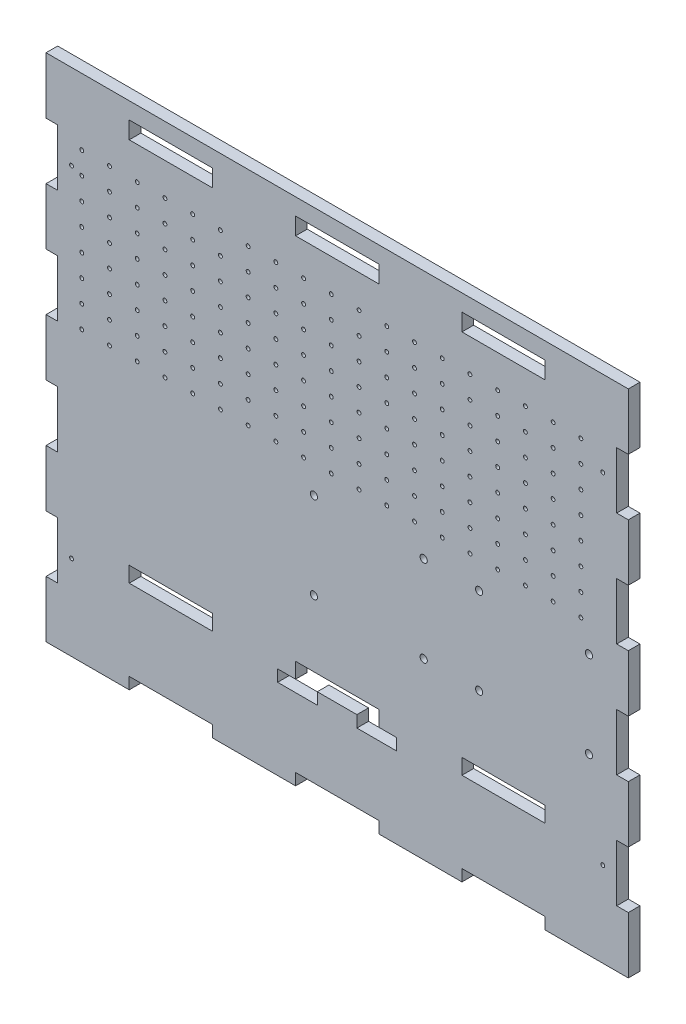
SolidWorks part; units mm, degrees
ref_plane "Front Plane" through (0, 0, 0) normal (0, 0, 1) x (1, 0, 0)
ref_plane "Top Plane" through (0, 0, 0) normal (0, 1, 0) x (1, 0, 0)
ref_plane "Right Plane" through (0, 0, 0) normal (1, 0, 0) x (0, 0, -1)
sketch "Sketch1" plane through (0, 0, 0) normal (0, 0, 1) x (1, 0, 0)
  line L1 (-127.8759, 139.2641) -> (138.8241, 139.2641)
  line L2 (-127.8759, 139.2641) -> (-127.8759, -84.2559)
  line L3 (-127.8759, -84.2559) -> (138.8241, -84.2559)
  line L4 (138.8241, 139.2641) -> (138.8241, -84.2559)
  dimension "D1" = 266.7
  dimension "D2" = 223.52
extrude "Boss-Extrude1" add sketch "Sketch1" along normal blind 5.334
sketch "Sketch2" plane through (0, 0, 5.334) normal (0, 0, 1) x (1, 0, 0)
  line L0 (-127.8759, -84.2559) -> (138.8241, -84.2559) construction
  line L1 (-89.7759, -84.2559) -> (-51.6759, -84.2559)
  line L2 (-89.7759, -84.2559) -> (-89.7759, -78.9219)
  line L3 (-89.7759, -78.9219) -> (-51.6759, -78.9219)
  line L4 (-51.6759, -84.2559) -> (-51.6759, -78.9219)
  line L5 (-89.7759, -78.9219) -> (-127.8759, -78.9219) construction
  line L6 (-13.5759, -84.2559) -> (24.5241, -84.2559)
  line L7 (-13.5759, -84.2559) -> (-13.5759, -78.9219)
  line L8 (-13.5759, -78.9219) -> (24.5241, -78.9219)
  line L9 (24.5241, -84.2559) -> (24.5241, -78.9219)
  line L10 (62.6241, -84.2559) -> (100.7241, -84.2559)
  line L11 (62.6241, -84.2559) -> (62.6241, -78.9219)
  line L12 (62.6241, -78.9219) -> (100.7241, -78.9219)
  line L13 (100.7241, -84.2559) -> (100.7241, -78.9219)
  line L14 (-127.8759, 139.2641) -> (-127.8759, -84.2559) construction
  line L15 (-51.6759, -78.9219) -> (-13.5759, -78.9219) construction
  line L16 (24.5241, -78.9219) -> (62.6241, -78.9219) construction
  line L17 (62.6241, -78.9219) -> (62.364, -79.7896) construction
  line L18 (100.7241, -78.9219) -> (138.8241, -78.9219) construction
  line L19 (138.8241, -84.2559) -> (138.8241, 139.2641) construction
  line L20 (-127.8759, 27.5041) -> (138.8241, 27.5041) construction
  line L21 (100.7241, 139.2641) -> (100.7241, 133.9301)
  line L22 (62.6241, 133.9301) -> (100.7241, 133.9301)
  line L23 (62.6241, 139.2641) -> (62.6241, 133.9301)
  line L24 (24.5241, 139.2641) -> (24.5241, 133.9301)
  line L25 (-13.5759, 133.9301) -> (24.5241, 133.9301)
  line L26 (-13.5759, 139.2641) -> (-13.5759, 133.9301)
  line L27 (-51.6759, 139.2641) -> (-51.6759, 133.9301)
  line L28 (-89.7759, 133.9301) -> (-51.6759, 133.9301)
  line L29 (-89.7759, 139.2641) -> (-89.7759, 133.9301)
  line L30 (62.6241, 139.2641) -> (100.7241, 139.2641)
  line L31 (-13.5759, 139.2641) -> (24.5241, 139.2641)
  line L32 (-89.7759, 139.2641) -> (-51.6759, 139.2641)
  dimension "D1" = 5.334
extrude "Cut-Extrude1" cut sketch "Sketch2" against normal through all
sketch "Sketch5" plane through (0, 0, 5.334) normal (0, 0, 1) x (1, 0, 0)
  line L0 (-51.6759, -34.8224) -> (-13.5759, -34.8224) construction
  line L1 (-89.7759, -34.8224) -> (-51.6759, -34.8224)
  line L2 (-89.7759, -34.8224) -> (-89.7759, -41.9344)
  line L3 (-89.7759, -41.9344) -> (-51.6759, -41.9344)
  line L4 (-51.6759, -34.8224) -> (-51.6759, -41.9344)
  line L5 (-13.5759, -34.8224) -> (24.5241, -34.8224)
  line L6 (-13.5759, -34.8224) -> (-13.5759, -41.9344)
  line L7 (-13.5759, -41.9344) -> (24.5241, -41.9344)
  line L8 (24.5241, -34.8224) -> (24.5241, -41.9344)
  line L9 (62.6241, -34.8224) -> (100.7241, -34.8224)
  line L10 (62.6241, -34.8224) -> (62.6241, -41.9344)
  line L11 (62.6241, -41.9344) -> (100.7241, -41.9344)
  line L12 (100.7241, -34.8224) -> (100.7241, -41.9344)
  line L13 (-51.6759, -41.9344) -> (-13.5759, -41.9344) construction
  line L14 (24.5241, -34.8224) -> (62.6241, -34.8224) construction
  line L15 (24.5241, -41.9344) -> (62.6241, -41.9344) construction
  line L16 (-89.7759, -34.8224) -> (-127.8759, -34.8224) construction
  line L17 (-127.8759, 139.2641) -> (-127.8759, -84.2559) construction
  line L18 (-89.7759, -41.9344) -> (-127.8759, -41.9344) construction
  line L19 (100.7241, -34.8224) -> (138.8241, -34.8224) construction
  line L20 (138.8241, -84.2559) -> (138.8241, 139.2641) construction
  line L21 (100.7241, -41.9344) -> (138.8241, -41.9344) construction
  dimension "D1" = 7.112
extrude "Cut-Extrude3" cut sketch "Sketch5" against normal through all
sketch "Sketch8" plane through (0, 0, 5.334) normal (0, 0, 1) x (1, 0, 0)
  line L0 (-13.5759, -41.9344) -> (24.5241, -41.9344) construction
  line L1 (-21.7977, -47.2684) -> (-3.6478, -47.2684)
  line L2 (-21.7977, -47.2684) -> (-21.7977, -41.9344)
  line L3 (-21.7977, -41.9344) -> (-3.6478, -41.9344)
  line L4 (-3.6478, -47.2684) -> (-3.6478, -41.9344)
  line L5 (-3.6478, -47.2684) -> (14.5022, -47.2684) construction
  line L6 (14.5022, -41.9344) -> (32.6521, -41.9344)
  line L7 (14.5022, -41.9344) -> (14.5022, -47.2684)
  line L8 (14.5022, -47.2684) -> (32.6521, -47.2684)
  line L9 (32.6521, -41.9344) -> (32.6521, -47.2684)
  line L10 (14.5022, -47.2684) -> (14.3218, -49.4005) construction
  line L11 (14.5022, -41.9344) -> (-3.6478, -41.9344) construction
  line L12 (62.6241, -34.8224) -> (62.6241, -41.9344) construction
  line L13 (-51.6759, -41.9344) -> (-51.6759, -34.8224) construction
  dimension "D1" = 5.334
  dimension "D2" = 29.972
  dimension "D3" = 29.8782
extrude "Cut-Extrude6" cut sketch "Sketch8" against normal through all
sketch "Sketch9" plane through (0, 0, 5.334) normal (0, 0, 1) x (1, 0, 0)
  line L0 (-111.5143, 118.9789) -> (-98.8143, 118.9789) construction
  line L1 (-111.5143, 108.8189) -> (-98.8143, 108.8189) construction
  line L2 (-111.5143, 98.6589) -> (-98.8143, 98.6589) construction
  line L3 (-111.5143, 88.4989) -> (-98.8143, 88.4989) construction
  line L4 (-111.5143, 78.3389) -> (-98.8143, 78.3389) construction
  line L5 (-111.5143, 68.1789) -> (-98.8143, 68.1789) construction
  line L6 (-111.5143, 58.0189) -> (-98.8143, 58.0189) construction
  line L7 (-111.5143, 47.8589) -> (-98.8143, 47.8589) construction
  line L8 (-111.5143, 118.9789) -> (-111.5143, 108.8189) construction
  circle A0 centre (-111.5143, 118.9789) radius 0.889
  circle A1 centre (-98.8143, 118.9789) radius 0.889
  circle A2 centre (-86.1143, 118.9789) radius 0.889
  circle A3 centre (-73.4143, 118.9789) radius 0.889
  circle A4 centre (-60.7143, 118.9789) radius 0.889
  circle A5 centre (-48.0143, 118.9789) radius 0.889
  circle A6 centre (-35.3143, 118.9789) radius 0.889
  circle A7 centre (-22.6143, 118.9789) radius 0.889
  circle A8 centre (-9.9143, 118.9789) radius 0.889
  circle A9 centre (2.7857, 118.9789) radius 0.889
  circle A10 centre (15.4857, 118.9789) radius 0.889
  circle A11 centre (28.1857, 118.9789) radius 0.889
  circle A12 centre (40.8857, 118.9789) radius 0.889
  circle A13 centre (53.5857, 118.9789) radius 0.889
  circle A14 centre (66.2857, 118.9789) radius 0.889
  circle A15 centre (78.9857, 118.9789) radius 0.889
  circle A16 centre (91.6857, 118.9789) radius 0.889
  circle A17 centre (104.3857, 118.9789) radius 0.889
  circle A18 centre (117.0857, 118.9789) radius 0.889
  circle A19 centre (-111.5143, 108.8189) radius 0.889
  circle A20 centre (-98.8143, 108.8189) radius 0.889
  circle A21 centre (-86.1143, 108.8189) radius 0.889
  circle A22 centre (-73.4143, 108.8189) radius 0.889
  circle A23 centre (-60.7143, 108.8189) radius 0.889
  circle A24 centre (-48.0143, 108.8189) radius 0.889
  circle A25 centre (-35.3143, 108.8189) radius 0.889
  circle A26 centre (-22.6143, 108.8189) radius 0.889
  circle A27 centre (-9.9143, 108.8189) radius 0.889
  circle A28 centre (2.7857, 108.8189) radius 0.889
  circle A29 centre (15.4857, 108.8189) radius 0.889
  circle A30 centre (28.1857, 108.8189) radius 0.889
  circle A31 centre (40.8857, 108.8189) radius 0.889
  circle A32 centre (53.5857, 108.8189) radius 0.889
  circle A33 centre (66.2857, 108.8189) radius 0.889
  circle A34 centre (78.9857, 108.8189) radius 0.889
  circle A35 centre (91.6857, 108.8189) radius 0.889
  circle A36 centre (104.3857, 108.8189) radius 0.889
  circle A37 centre (117.0857, 108.8189) radius 0.889
  circle A38 centre (-111.5143, 98.6589) radius 0.889
  circle A39 centre (-98.8143, 98.6589) radius 0.889
  circle A40 centre (-86.1143, 98.6589) radius 0.889
  circle A41 centre (-73.4143, 98.6589) radius 0.889
  circle A42 centre (-60.7143, 98.6589) radius 0.889
  circle A43 centre (-48.0143, 98.6589) radius 0.889
  circle A44 centre (-35.3143, 98.6589) radius 0.889
  circle A45 centre (-22.6143, 98.6589) radius 0.889
  circle A46 centre (-9.9143, 98.6589) radius 0.889
  circle A47 centre (2.7857, 98.6589) radius 0.889
  circle A48 centre (15.4857, 98.6589) radius 0.889
  circle A49 centre (28.1857, 98.6589) radius 0.889
  circle A50 centre (40.8857, 98.6589) radius 0.889
  circle A51 centre (53.5857, 98.6589) radius 0.889
  circle A52 centre (66.2857, 98.6589) radius 0.889
  circle A53 centre (78.9857, 98.6589) radius 0.889
  circle A54 centre (91.6857, 98.6589) radius 0.889
  circle A55 centre (104.3857, 98.6589) radius 0.889
  circle A56 centre (117.0857, 98.6589) radius 0.889
  circle A57 centre (-111.5143, 88.4989) radius 0.889
  circle A58 centre (-98.8143, 88.4989) radius 0.889
  circle A59 centre (-86.1143, 88.4989) radius 0.889
  circle A60 centre (-73.4143, 88.4989) radius 0.889
  circle A61 centre (-60.7143, 88.4989) radius 0.889
  circle A62 centre (-48.0143, 88.4989) radius 0.889
  circle A63 centre (-35.3143, 88.4989) radius 0.889
  circle A64 centre (-22.6143, 88.4989) radius 0.889
  circle A65 centre (-9.9143, 88.4989) radius 0.889
  circle A66 centre (2.7857, 88.4989) radius 0.889
  circle A67 centre (15.4857, 88.4989) radius 0.889
  circle A68 centre (28.1857, 88.4989) radius 0.889
  circle A69 centre (40.8857, 88.4989) radius 0.889
  circle A70 centre (53.5857, 88.4989) radius 0.889
  circle A71 centre (66.2857, 88.4989) radius 0.889
  circle A72 centre (78.9857, 88.4989) radius 0.889
  circle A73 centre (91.6857, 88.4989) radius 0.889
  circle A74 centre (104.3857, 88.4989) radius 0.889
  circle A75 centre (117.0857, 88.4989) radius 0.889
  circle A76 centre (-111.5143, 78.3389) radius 0.889
  circle A77 centre (-98.8143, 78.3389) radius 0.889
  circle A78 centre (-86.1143, 78.3389) radius 0.889
  circle A79 centre (-73.4143, 78.3389) radius 0.889
  circle A80 centre (-60.7143, 78.3389) radius 0.889
  circle A81 centre (-48.0143, 78.3389) radius 0.889
  circle A82 centre (-35.3143, 78.3389) radius 0.889
  circle A83 centre (-22.6143, 78.3389) radius 0.889
  circle A84 centre (-9.9143, 78.3389) radius 0.889
  circle A85 centre (2.7857, 78.3389) radius 0.889
  circle A86 centre (15.4857, 78.3389) radius 0.889
  circle A87 centre (28.1857, 78.3389) radius 0.889
  circle A88 centre (40.8857, 78.3389) radius 0.889
  circle A89 centre (53.5857, 78.3389) radius 0.889
  circle A90 centre (66.2857, 78.3389) radius 0.889
  circle A91 centre (78.9857, 78.3389) radius 0.889
  circle A92 centre (91.6857, 78.3389) radius 0.889
  circle A93 centre (104.3857, 78.3389) radius 0.889
  circle A94 centre (117.0857, 78.3389) radius 0.889
  circle A95 centre (-111.5143, 68.1789) radius 0.889
  circle A96 centre (-98.8143, 68.1789) radius 0.889
  circle A97 centre (-86.1143, 68.1789) radius 0.889
  circle A98 centre (-73.4143, 68.1789) radius 0.889
  circle A99 centre (-60.7143, 68.1789) radius 0.889
  circle A100 centre (-48.0143, 68.1789) radius 0.889
  circle A101 centre (-35.3143, 68.1789) radius 0.889
  circle A102 centre (-22.6143, 68.1789) radius 0.889
  circle A103 centre (-9.9143, 68.1789) radius 0.889
  circle A104 centre (2.7857, 68.1789) radius 0.889
  circle A105 centre (15.4857, 68.1789) radius 0.889
  circle A106 centre (28.1857, 68.1789) radius 0.889
  circle A107 centre (40.8857, 68.1789) radius 0.889
  circle A108 centre (53.5857, 68.1789) radius 0.889
  circle A109 centre (66.2857, 68.1789) radius 0.889
  circle A110 centre (78.9857, 68.1789) radius 0.889
  circle A111 centre (91.6857, 68.1789) radius 0.889
  circle A112 centre (104.3857, 68.1789) radius 0.889
  circle A113 centre (117.0857, 68.1789) radius 0.889
  circle A114 centre (-111.5143, 58.0189) radius 0.889
  circle A115 centre (-98.8143, 58.0189) radius 0.889
  circle A116 centre (-86.1143, 58.0189) radius 0.889
  circle A117 centre (-73.4143, 58.0189) radius 0.889
  circle A118 centre (-60.7143, 58.0189) radius 0.889
  circle A119 centre (-48.0143, 58.0189) radius 0.889
  circle A120 centre (-35.3143, 58.0189) radius 0.889
  circle A121 centre (-22.6143, 58.0189) radius 0.889
  circle A122 centre (-9.9143, 58.0189) radius 0.889
  circle A123 centre (2.7857, 58.0189) radius 0.889
  circle A124 centre (15.4857, 58.0189) radius 0.889
  circle A125 centre (28.1857, 58.0189) radius 0.889
  circle A126 centre (40.8857, 58.0189) radius 0.889
  circle A127 centre (53.5857, 58.0189) radius 0.889
  circle A128 centre (66.2857, 58.0189) radius 0.889
  circle A129 centre (78.9857, 58.0189) radius 0.889
  circle A130 centre (91.6857, 58.0189) radius 0.889
  circle A131 centre (104.3857, 58.0189) radius 0.889
  circle A132 centre (117.0857, 58.0189) radius 0.889
  circle A133 centre (-111.5143, 47.8589) radius 0.889
  circle A134 centre (-98.8143, 47.8589) radius 0.889
  circle A135 centre (-86.1143, 47.8589) radius 0.889
  circle A136 centre (-73.4143, 47.8589) radius 0.889
  circle A137 centre (-60.7143, 47.8589) radius 0.889
  circle A138 centre (-48.0143, 47.8589) radius 0.889
  circle A139 centre (-35.3143, 47.8589) radius 0.889
  circle A140 centre (-22.6143, 47.8589) radius 0.889
  circle A141 centre (-9.9143, 47.8589) radius 0.889
  circle A142 centre (2.7857, 47.8589) radius 0.889
  circle A143 centre (15.4857, 47.8589) radius 0.889
  circle A144 centre (28.1857, 47.8589) radius 0.889
  circle A145 centre (40.8857, 47.8589) radius 0.889
  circle A146 centre (53.5857, 47.8589) radius 0.889
  circle A147 centre (66.2857, 47.8589) radius 0.889
  circle A148 centre (78.9857, 47.8589) radius 0.889
  circle A149 centre (91.6857, 47.8589) radius 0.889
  circle A150 centre (104.3857, 47.8589) radius 0.889
  circle A151 centre (117.0857, 47.8589) radius 0.889
  dimension "D1" = 19
  dimension "D5" = 1.778
  dimension "D2" = 12.7
  dimension "D4" = 10.16
  dimension "D3" = 8
extrude "Cut-Extrude7" cut sketch "Sketch9" against normal through all
sketch "Sketch10" plane through (0, 139.2641, 0) normal (0, 1, 0) x (1, 0, 0)
  line L0 (-13.5759, -5.334) -> (-51.6759, -5.334) construction
  line L1 (-51.6759, 0) -> (-13.5759, 0)
  line L2 (-51.6759, 0) -> (-51.6759, -5.334)
  line L3 (-51.6759, -5.334) -> (-13.5759, -5.334)
  line L4 (-13.5759, 0) -> (-13.5759, -5.334)
extrude "Boss-Extrude2" add sketch "Sketch10" along normal blind 10.16
sketch "Sketch12" plane through (-51.6759, 0, 0) normal (-1, 0, 0) x (0, 0, 1)
  line L0 (0, 133.9301) -> (0, 149.4241) construction
  line L1 (5.334, 149.4241) -> (0, 149.4241)
  line L2 (5.334, 149.4241) -> (5.334, 141.8041)
  line L3 (5.334, 141.8041) -> (0, 141.8041)
  line L4 (0, 149.4241) -> (0, 141.8041)
  dimension "D1" = 7.62
extrude "Boss-Extrude3" add sketch "Sketch12" along normal blind 76.2 and the other way blind 190.5
sketch "Sketch13" plane through (0, 139.2641, 0) normal (0, 1, 0) x (1, 0, 0)
  line L1 (-127.8759, 0) -> (-89.7759, 0)
  line L2 (-127.8759, 0) -> (-127.8759, -5.334)
  line L3 (-127.8759, -5.334) -> (-89.7759, -5.334)
  line L4 (-89.7759, 0) -> (-89.7759, -5.334)
extrude "Boss-Extrude4" add sketch "Sketch13" along normal blind 2.54
sketch "Sketch14" plane through (0, 139.2641, 0) normal (0, 1, 0) x (1, 0, 0)
  line L1 (24.5241, 0) -> (62.6241, 0)
  line L2 (24.5241, 0) -> (24.5241, -5.334)
  line L3 (24.5241, -5.334) -> (62.6241, -5.334)
  line L4 (62.6241, 0) -> (62.6241, -5.334)
extrude "Boss-Extrude5" add sketch "Sketch14" along normal blind 2.54
sketch "Sketch15" plane through (0, 139.2641, 0) normal (0, 1, 0) x (1, 0, 0)
  line L1 (100.7241, 0) -> (138.8241, 0)
  line L2 (100.7241, 0) -> (100.7241, -5.334)
  line L3 (100.7241, -5.334) -> (138.8241, -5.334)
  line L4 (138.8241, 0) -> (138.8241, -5.334)
extrude "Boss-Extrude6" add sketch "Sketch15" along normal blind 2.54
sketch "Sketch16" plane through (0, 0, 5.334) normal (0, 0, 1) x (1, 0, 0)
  line L0 (-127.8759, 149.4241) -> (-127.8759, -84.2559) construction
  line L1 (-127.8759, -32.327) -> (-122.5419, -32.327)
  line L2 (-127.8759, -32.327) -> (-127.8759, -58.2914)
  line L3 (-127.8759, -58.2914) -> (-122.5419, -58.2914)
  line L4 (-122.5419, -32.327) -> (-122.5419, -58.2914)
  line L5 (-122.5419, -32.327) -> (-122.5419, -6.3625) construction
  line L6 (-127.8759, 19.6019) -> (-122.5419, 19.6019)
  line L7 (-122.5419, -58.2914) -> (-122.5419, -84.2559) construction
  line L8 (-127.8759, -84.2559) -> (-89.7759, -84.2559) construction
  line L9 (-127.8759, 19.6019) -> (-127.8759, -6.3625)
  line L10 (-127.8759, -6.3625) -> (-122.5419, -6.3625)
  line L11 (-122.5419, 19.6019) -> (-122.5419, -6.3625)
  line L12 (-122.5419, 19.6019) -> (-122.5419, 45.5664) construction
  line L13 (5.4741, -78.9219) -> (5.4741, 149.4241) construction
  line L14 (-127.8759, 71.5308) -> (-122.5419, 71.5308)
  line L15 (-127.8759, 71.5308) -> (-127.8759, 45.5664)
  line L16 (-127.8759, 45.5664) -> (-122.5419, 45.5664)
  line L17 (-122.5419, 71.5308) -> (-122.5419, 45.5664)
  line L18 (-122.5419, 71.5308) -> (-122.5419, 97.4953) construction
  line L19 (24.5241, -78.9219) -> (-13.5759, -78.9219) construction
  line L20 (-127.8759, 97.4953) -> (-122.5419, 97.4953)
  line L21 (-127.8759, 97.4953) -> (-127.8759, 123.4597)
  line L22 (-127.8759, 123.4597) -> (-122.5419, 123.4597)
  line L23 (-122.5419, 97.4953) -> (-122.5419, 123.4597)
  line L24 (-122.5419, 123.4597) -> (-122.5419, 149.4241) construction
  line L25 (-127.8759, 149.4241) -> (138.8241, 149.4241) construction
  line L26 (133.4901, 123.4597) -> (133.4901, 149.4241) construction
  line L27 (133.4901, 71.5308) -> (133.4901, 97.4953) construction
  line L28 (133.4901, 19.6019) -> (133.4901, 45.5664) construction
  line L29 (133.4901, -58.2914) -> (133.4901, -84.2559) construction
  line L30 (133.4901, -32.327) -> (133.4901, -6.3625) construction
  line L31 (133.4901, 97.4953) -> (133.4901, 123.4597)
  line L32 (138.8241, 123.4597) -> (133.4901, 123.4597)
  line L33 (138.8241, 97.4953) -> (138.8241, 123.4597)
  line L34 (138.8241, 97.4953) -> (133.4901, 97.4953)
  line L35 (133.4901, 71.5308) -> (133.4901, 45.5664)
  line L36 (138.8241, 45.5664) -> (133.4901, 45.5664)
  line L37 (138.8241, 71.5308) -> (138.8241, 45.5664)
  line L38 (138.8241, 71.5308) -> (133.4901, 71.5308)
  line L39 (133.4901, 19.6019) -> (133.4901, -6.3625)
  line L40 (138.8241, -6.3625) -> (133.4901, -6.3625)
  line L41 (138.8241, 19.6019) -> (138.8241, -6.3625)
  line L42 (138.8241, 19.6019) -> (133.4901, 19.6019)
  line L43 (133.4901, -32.327) -> (133.4901, -58.2914)
  line L44 (138.8241, -58.2914) -> (133.4901, -58.2914)
  line L45 (138.8241, -32.327) -> (138.8241, -58.2914)
  line L46 (138.8241, -32.327) -> (133.4901, -32.327)
  dimension "D1" = 5.334
extrude "Cut-Extrude9" cut sketch "Sketch16" against normal through all
sketch "Sketch17" plane through (0, 0, 5.334) normal (0, 0, 1) x (1, 0, 0)
  line L1 (133.4901, 71.5308) -> (133.4901, 45.5664) construction
  circle A0 centre (120.7901, 35.1589) radius 1.651
  circle A1 centre (117.0857, 47.8589) radius 0.889 construction
  circle A2 centre (70.4981, 35.1589) radius 1.651
  circle A3 centre (70.4981, -4.4651) radius 1.651
  circle A4 centre (120.7901, -4.4651) radius 1.651
  circle A5 centre (45.0981, 35.1589) radius 1.651
  circle A6 centre (-5.1939, 35.1589) radius 1.651
  circle A7 centre (-5.1939, -4.4651) radius 1.651
  circle A8 centre (45.0981, -4.4651) radius 1.651
  dimension "D1" = 12.7
  dimension "D2" = 12.7
  dimension "D3" = 2
  dimension "D4" = 2
  dimension "D5" = 2
  dimension "D6" = 2
  dimension "D7" = 2
extrude "Cut-Extrude10" cut sketch "Sketch17" against normal through all
sketch "Sketch18" plane through (0, 0, 5.334) normal (0, 0, 1) x (1, 0, 0)
  line L0 (133.4901, 123.4597) -> (133.4901, 97.4953) construction
  line L1 (133.4901, 110.4775) -> (-122.5419, 110.4775) construction
  line L2 (-122.5419, 97.4953) -> (-122.5419, 123.4597) construction
  line L3 (-122.5419, -45.3092) -> (133.4901, -45.3092) construction
  line L4 (-122.5419, -58.2914) -> (-122.5419, -32.327) construction
  line L5 (133.4901, -32.327) -> (133.4901, -58.2914) construction
  line L6 (138.8241, 32.5841) -> (-127.8759, 32.5841) construction
  line L7 (138.8241, 19.6019) -> (138.8241, 45.5664) construction
  line L8 (-127.8759, 45.5664) -> (-127.8759, 19.6019) construction
  line L9 (5.4741, 149.4241) -> (5.4741, -78.9219) construction
  line L10 (-127.8759, 149.4241) -> (138.8241, 149.4241) construction
  line L11 (24.5241, -78.9219) -> (-13.5759, -78.9219) construction
  circle A0 centre (127.1401, 110.4775) radius 0.889
  circle A1 centre (-116.1919, 110.4775) radius 0.889
  circle A2 centre (-116.1919, -45.3092) radius 0.889
  circle A3 centre (127.1401, -45.3092) radius 0.889
  point P2 (133.4901, 110.4775)
  dimension "D3" = 1.778
  dimension "D1" = 0
  dimension "D2" = 6.35
extrude "Cut-Extrude11" cut sketch "Sketch18" against normal through all
equation "\"MDF\"= .21in"
equation "\"Foamcore\"= .13in"
equation "\"Gmaterial\"= \"MDF\""
equation "\"D1@Boss-Extrude1\"=\"MDF\""
equation "\"D1@Sketch2\"=\"MDF\""
equation "\"D1@Sketch5\"=\"MDF\"+0.07"
equation "\"D1@Sketch8\"=\"MDF\""
equation "\"D1@Sketch16\"=\"MDF\""
